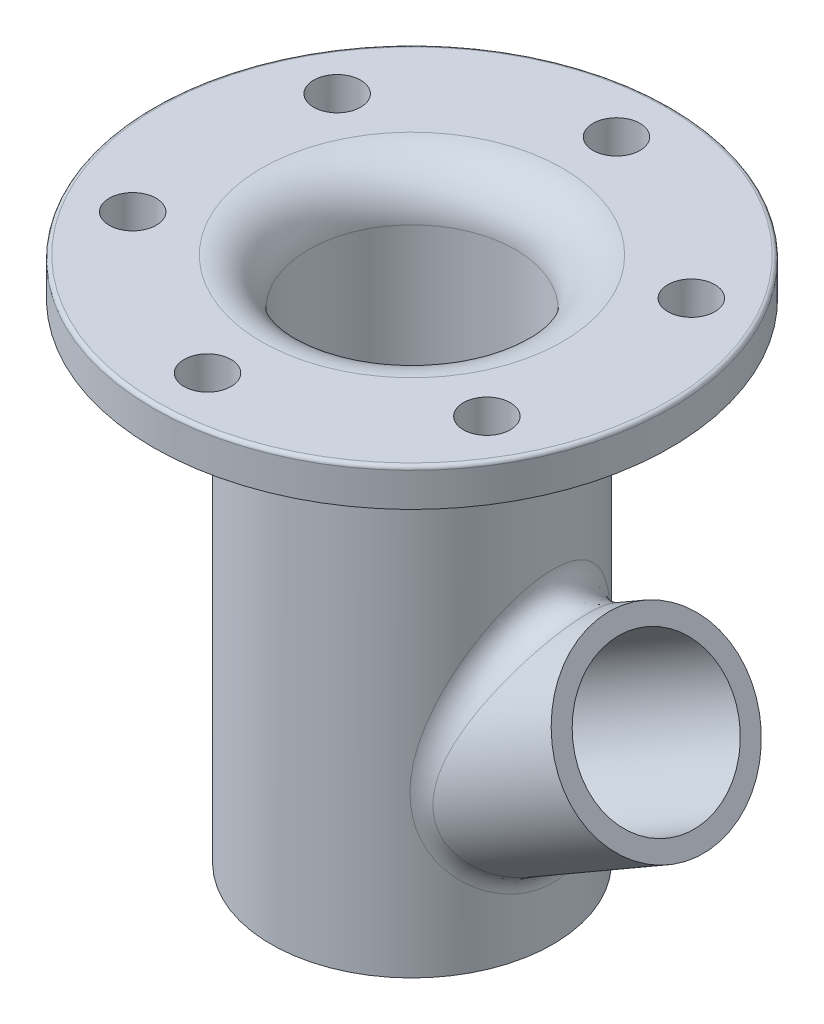
SolidWorks part; units mm, degrees
ref_plane "Front Plane" through (0, 0, 0) normal (0, 0, 1) x (1, 0, 0)
ref_plane "Top Plane" through (0, 0, 0) normal (0, 1, 0) x (1, 0, 0)
ref_plane "Right Plane" through (0, 0, 0) normal (1, 0, 0) x (0, 0, -1)
sketch "Sketch1" plane through (0, 0, 0) normal (0, 0, 1) x (1, 0, 0)
  line L0 (-8.4447, 61.3229) -> (-20.955, 61.3229)
  line L1 (-20.955, 61.3229) -> (-20.955, 56.2429)
  line L2 (-20.955, 56.2429) -> (-5.08, 56.2429)
  line L3 (-5.08, 56.2429) -> (-5.08, -9.7971)
  line L4 (-5.08, -9.7971) -> (0, -9.7971)
  line L5 (0, -4.7171) -> (0, 61.3229)
  line L6 (0, 61.3229) -> (-8.4447, 61.3229)
  line L7 (13.97, -9.7971) -> (13.97, 61.3229) construction
  line L11 (0, -4.7171) -> (0, -9.7971)
  dimension "D1" = 5.08
  dimension "D2" = 71.12
  dimension "D3" = 5.08
  dimension "D4" = 19.05
  dimension "D6" = 34.925
revolve "Revolve2" add sketch "Sketch1" angle 360 about L7
fillet "Fillet1" radius 6.35 1 edges at (13.97, 61.3229, -13.97)
ref_plane "Plane1" through (0, 61.3229, 0) normal (0, 1, 0) x (1, 0, 0)
sketch "Sketch3" plane through (0, 61.3229, 0) normal (0, 1, 0) x (1, 0, 0)
  line L0 (13.97, 34.925) -> (13.97, 20.32) construction
  circle A0 centre (13.97, 0) radius 34.925 construction
  circle A1 centre (13.97, 0) radius 20.32 construction
  circle A2 centre (13.97, 27.6225) radius 3.175
  dimension "D1" = 6.35
extrude "Cut-Extrude1" cut sketch "Sketch3" against normal up to next
pattern_circular "CirPattern1" count 6 over 360 about axis through (13.97, -9.7971, 0) along (0, -1, 0) of "Cut-Extrude1"
fillet "Fillet2" radius 0.508 1 edges at (13.97, 61.3229, -34.925)
sketch "Sketch4" plane through (0, 0, 0) normal (0, 0, 1) x (1, 0, 0)
  line L0 (13.97, -9.7971) -> (13.97, 60.8149) construction
  line L1 (-5.08, -9.7971) -> (33.02, -9.7971) construction
  line L2 (48.895, 60.8149) -> (-20.955, 60.8149) construction
  line L3 (13.97, 2.9029) -> (46.9656, 21.9529) construction
  line L4 (13.97, 2.9029) -> (80.3007, 2.9029) construction
  dimension "D1" = 12.7
  dimension "D2" = 30
  dimension "D3" = 38.1
ref_plane "Plane2" through (46.9656, 21.9529, 0) normal (0.866, 0.5, 0) x (0, 0, -1)
sketch "Sketch5" plane through (46.9656, 21.9529, 0) normal (0.866, 0.5, 0) x (0, 0, -1)
  line L0 (0, 0) -> (0, -33.1654) construction
  line L1 (0, -10.9985) -> (0, 50.1533) construction
  circle A0 centre (0, 0) radius 12.7
  dimension "D1" = 25.4
extrude "Boss-Extrude1" add sketch "Sketch5" against normal up to next
sketch "Sketch6" plane through (46.9656, 21.9529, 0) normal (0.866, 0.5, 0) x (0, 0, -1)
  line L0 (0, 0) -> (0, -33.1654) construction
  line L1 (0, -10.9985) -> (0, 50.1533) construction
  circle A0 centre (0, 0) radius 10.16
  dimension "D1" = 20.32
extrude "Cut-Extrude2" cut sketch "Sketch6" against normal up to next
fillet "Fillet3" radius 3.175 2 edges at (13.97, 56.2429, -19.05) (32.8517, -0.5674, -2.5263)
